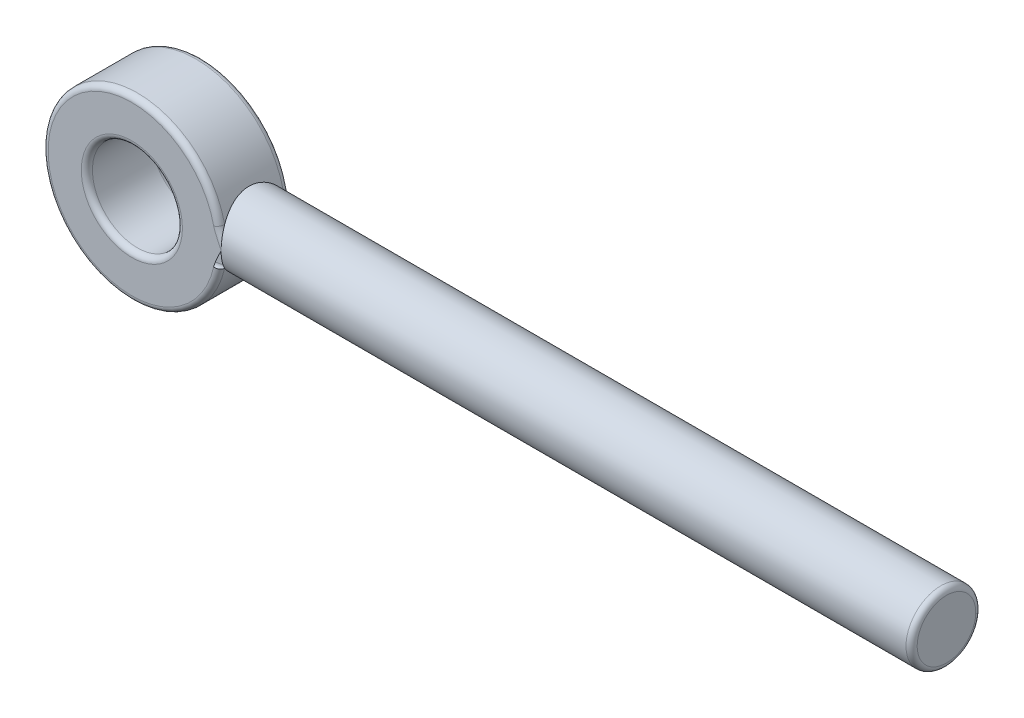
SolidWorks part; units mm, degrees
ref_plane "Front Plane" through (0, 0, 0) normal (0, 0, 1) x (1, 0, 0)
ref_plane "Top Plane" through (0, 0, 0) normal (0, 1, 0) x (1, 0, 0)
ref_plane "Right Plane" through (0, 0, 0) normal (1, 0, 0) x (0, 0, -1)
sketch "Sketch1" plane through (0, 0, 0) normal (0, 1, 0) x (1, 0, 0)
  line L0 (0, 0) -> (63.5, 0) construction
  line L1 (0, 0) -> (0, 3.175)
  line L2 (0, 3.175) -> (63.5, 3.175)
  line L3 (0, 0) -> (63.5, 0)
  line L4 (63.5, 3.175) -> (63.5, 0)
  dimension "D1" = 3.175
  dimension "D2" = 63.5
revolve "Revolve1" add sketch "Sketch1" angle 360 about L0
sketch "Sketch2" plane through (0, 0, 0) normal (0, 0, 1) x (1, 0, 0)
  circle A0 centre (-7.4822, 0) radius 4.0957
  circle A1 centre (-7.4822, 0) radius 8.128
  dimension "D1" = 8.1915
  dimension "D2" = 16.256
extrude "Boss-Extrude1" add sketch "Sketch2" along normal mid plane 6.35
ref_axis "Axis1" through (63.5, 0, 0) along (-1, 0, 0)
fillet "Fillet1" radius 0.508 5 edges at (-3.3865, 0, -3.175) (-3.3865, 0, 3.175) (63.5, 0, 3.175) (0.6458, 0, -3.175) (0.6458, 0, 3.175)
